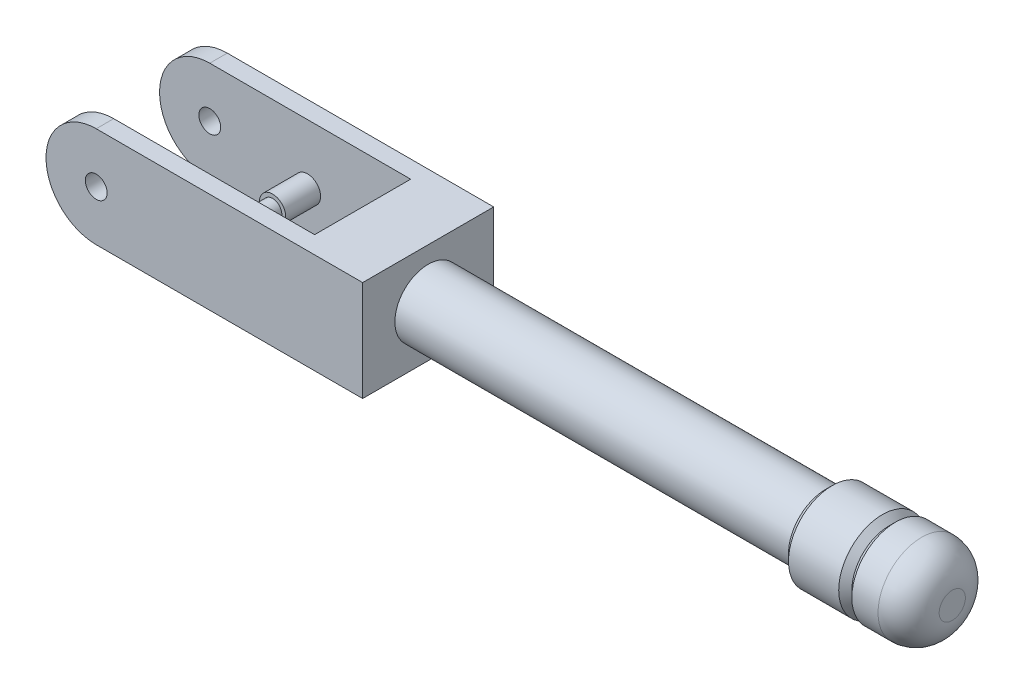
SolidWorks part; units mm, degrees
ref_plane "Alzado" through (0, 0, 0) normal (0, 0, 1) x (1, 0, 0)
ref_plane "Planta" through (0, 0, 0) normal (0, 1, 0) x (1, 0, 0)
ref_plane "Vista lateral" through (0, 0, 0) normal (1, 0, 0) x (0, 0, -1)
other "Centro de masa"
ref_plane "Plano1" through (0, 0, 30) normal (0, 0, 1) x (1, 0, 0)
sketch "Croquis1" plane through (0, 0, 30) normal (0, 0, 1) x (1, 0, 0)
  line L1 (122, -23) -> (122, 23)
  line L2 (0, 23) -> (122, 23)
  line L3 (122, -23) -> (0, -23)
  arc A0 (0, 23) -> (0, -23) centre (0, 0) ccw
  dimension "D2" = 23
  dimension "D1" = 122
  dimension "D3" = 46
extrude "Saliente-Extruir1" add sketch "Croquis1" against normal blind 60
sketch "Croquis3" plane through (0, 23, 0) normal (0, 1, 0) x (1, 0, 0)
  line L0 (122, 0) -> (-40.0018, 0) construction
  line L1 (122, 30) -> (122, -30) construction
  line L2 (-23, 30) -> (-23, -30) construction
  line L3 (92, 22) -> (-23, 22)
  line L4 (92, 22) -> (92, -22)
  line L5 (92, -22) -> (-23, -22)
  line L6 (-23, 22) -> (-23, -22)
  line L7 (122, 30) -> (0, 30) construction
  dimension "D1" = 8
  dimension "D2" = 30
extrude "Cortar-Extruir1" cut sketch "Croquis3" against normal up to next
sketch "Croquis4" plane through (0, 0, 30) normal (0, 0, 1) x (1, 0, 0)
  circle A0 centre (0, 0) radius 21
  dimension "D1" = 42
extrude "Saliente-Extruir2" [suppressed] add sketch "Croquis4" along normal blind 5.5
sketch "Croquis5" [suppressed] plane through (0, 0, -30) normal (0, 0, -1) x (-1, 0, 0)
  circle A0 centre (0, 0) radius 21 construction
  circle A1 centre (0, 0) radius 21
extrude "Saliente-Extruir3" [suppressed] add sketch "Croquis5" along normal blind 5.5
sketch "Croquis6" plane through (0, 0, -22) normal (0, 0, 1) x (1, 0, 0)
  line L0 (122, 0) -> (0, 0) construction
  line L1 (122, -23) -> (122, 23) construction
  line L2 (92, -23) -> (92, 23) construction
  circle A0 centre (44.75, -4.5) radius 6
  dimension "D1" = 12
  dimension "D2" = 47.25
  dimension "D3" = 4.5
extrude "Saliente-Extruir4" add sketch "Croquis6" along normal blind 16
sketch "Croquis7" plane through (0, 0, -6) normal (0, 0, 1) x (1, 0, 0)
  circle A0 centre (44.75, -4.5) radius 4.25
  dimension "D1" = 8.5
extrude "Saliente-Extruir5" add sketch "Croquis7" along normal blind 12
sketch "Croquis8" plane through (0, 0, 6) normal (0, 0, 1) x (1, 0, 0)
  circle A0 centre (44.75, -4.5) radius 6 construction
  circle A1 centre (44.75, -4.5) radius 6
extrude "Saliente-Extruir6" add sketch "Croquis8" along normal up to next
sketch "Croquis9" plane through (122, 0, 0) normal (1, 0, 0) x (0, 0, -1)
  line L0 (0, 23) -> (0, -23) construction
  line L1 (30, 23) -> (-30, 23) construction
  line L2 (30, -23) -> (-30, -23) construction
  circle A0 centre (0, 0) radius 15.25
  dimension "D1" = 30.5
extrude "Saliente-Extruir7" add sketch "Croquis9" along normal blind 182
sketch "Croquis10" plane through (304, 0, 0) normal (1, 0, 0) x (0, 0, -1)
  circle A0 centre (0, 0) radius 20
  dimension "D1" = 40
extrude "Saliente-Extruir8" add sketch "Croquis10" along normal blind 29
chamfer "Chaflán1" distance 3 angle 45 1 edges at (304, 0, -20)
chamfer "Chaflán2" distance 3 angle 45 1 edges at (333, 0, -20)
sketch "Croquis11" plane through (333, 0, 0) normal (1, 0, 0) x (0, 0, -1)
  circle A0 centre (0, 0) radius 20 construction
  circle A1 centre (0, 0) radius 20
extrude "Saliente-Extruir9" add sketch "Croquis11" along normal blind 29
chamfer "Chaflán3" distance 3 angle 45 1 edges at (333, 0, -20)
fillet "Redondeo1" radius 14 1 edges at (362, 0, -20)
sketch "Croquis12" plane through (0, 0, 30) normal (0, 0, 1) x (1, 0, 0)
  circle A0 centre (0, 0) radius 5
  dimension "D1" = 10
extrude "Cortar-Extruir2" cut sketch "Croquis12" against normal through all
